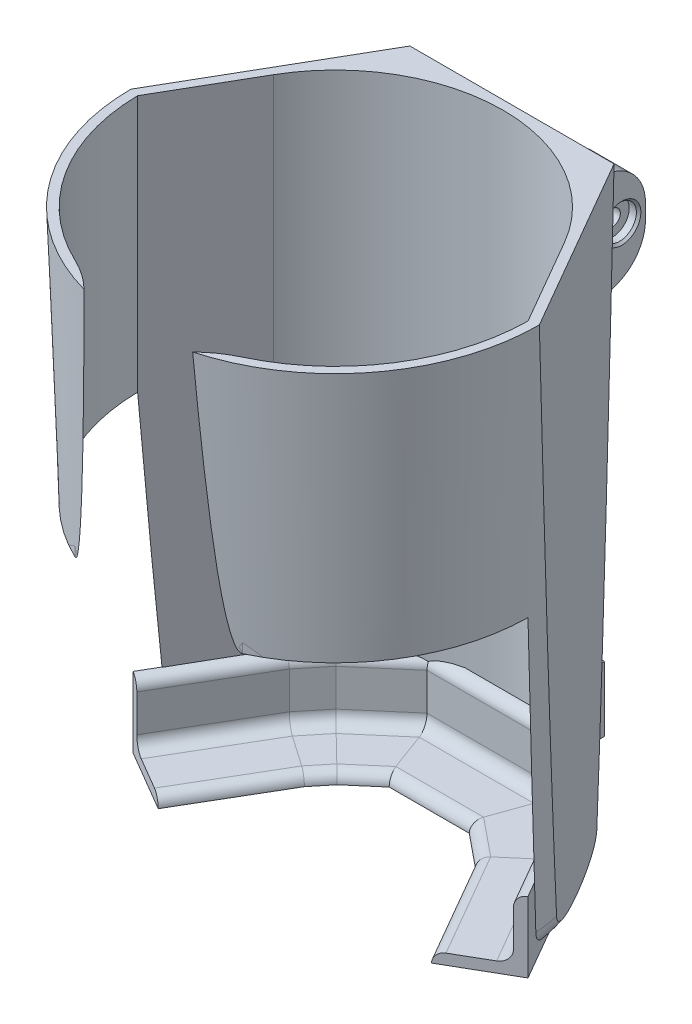
SolidWorks part; units mm, degrees
note: '?' marks a value the reader was unsure of. The reader was unsure of these and kept them because the rebuilt part matched: shared geometry of "Sketch1<3>", "Sketch1<4>", "Sketch1<9>".
ref_plane "Front Plane" through (0, 0, 0) normal (0, 0, 1) x (1, 0, 0)
ref_plane "Top Plane" through (0, 0, 0) normal (0, 1, 0) x (1, 0, 0)
ref_plane "Right Plane" through (0, 0, 0) normal (1, 0, 0) x (0, 0, -1)
sketch "Sketch1" plane through (0, 0, 0) normal (0, 1, 0) x (1, 0, 0)
  line L0 (55.2877, -0.6735) -> (27.4494, 47.5438)
  line L1 (57.8318, 0) -> (28.9159, 50.0838)
  line L2 (28.9159, 50.0838) -> (-28.9159, 50.0838)
  line L3 (-28.9159, 50.0838) -> (-57.8318, 0)
  line L7 (0, -50.0838) -> (28.9159, -50.0838) [skipped]
  line L8 (43.3739, -25.0419) -> (57.8318, 0) [skipped]
  line L9 (-57.8318, 0) -> (-43.3739, -25.0419) [skipped]
  line L10 (27.4494, 47.5438) -> (-27.4494, 47.5438)
  line L11 (-27.4494, 47.5438) -> (-55.2877, -0.6735)
  line L12 (0, -2.9319) -> (0, 50.0838) construction
  line L13 (-55.2877, -0.6735) -> (55.2877, -0.6735)
  arc A0 (-57.8318, 0) -> (57.8318, 0) centre (0, 0) ccw
  arc A1 (43.3739, 25.0419) -> (-43.3739, 25.0419) centre (0, 0) ccw construction
  arc A2 (-55.2877, -0.6735) -> (55.2877, -0.6735) centre (0, 0) ccw
  arc A3 (41.1742, 23.7719) -> (-41.1742, 23.7719) centre (0, 0) ccw
  arc A4 (-55.2877, -0.6735) -> (-23.6852, -49.962) centre (0, 0) ccw
  arc A5 (-23.6852, -49.962) -> (-15.381, -55.7489) centre (-36.8096, -77.6469) cw
  arc A6 (23.6852, -49.962) -> (15.381, -55.7489) centre (36.8096, -77.6469) ccw
  arc A7 (55.2877, -0.6735) -> (23.6852, -49.962) centre (0, 0) cw
  dimension "D1" = 115.6636
  dimension "D2" = 2.54
ref_axis "Axis2" through (0, 0, 0) along (0, 1, 0)?
ref_plane "Plane1" through (0, 0, 0) normal (0, 0, 1) x (1, 0, 0)
sketch "Sketch2" plane through (0, 0, 0) normal (0, 0, 1) x (1, 0, 0)
  line L0 (-57.8318, 0) -> (-52.4478, -154.178)
  line L1 (57.8318, 0) -> (-57.8318, 0) construction
  line L2 (-28.9159, 0) -> (-57.8318, 0) construction
  line L3 (-44.6574, -161.7011) -> (0, -161.7011)
  line L5 (0, 0) -> (-57.8318, 0)
  line L6 (0, -161.7011) -> (0, 0) construction
  line L7 (27.4494, 0) -> (-27.4494, 0) construction
  line L8 (0, 0) -> (0, -161.7011)
  arc A1 (-44.6574, -161.7011) -> (-52.4478, -154.178) centre (-44.6574, -153.906) cw
  point P11 (52.1851, -161.7011)
  point P14 (-52.1851, -161.7011)
  dimension "D1" = 92
  dimension "D4" = 161.7011
revolve "Revolve11" add sketch "Sketch2" angle 360 about L6
extrude "Cut-Extrude2" cut sketch "Sketch1" against normal blind 165.1 flip side to cut contours L1 L2 L3 A0
sketch "Sketch3" plane through (0, 0, 0) normal (0, 1, 0) x (1, 0, 0)
  circle A0 centre (0, 0) radius 46.5032
  circle A1 centre (0, 0) radius 49.0432 construction
  circle A2 centre (0, 0) radius 49.0432
  dimension "D1" = 93.0063
  dimension "D2" = 2.54
ref_plane "Plane2" through (0, 6.35, 0) normal (0, 1, 0) x (1, 0, 0)
extrude "Boss-Extrude1" add sketch "Sketch1<3>" against normal blind 149.606 contours A7 L13 A4 A5 A0 A6
sketch "Sketch1<3>" plane through (0, 0, 0) normal (0, 1, 0) x (1, 0, 0) same geometry as "Sketch1"
extrude "Cut-Extrude9" cut sketch "Sketch1<4>" along direction (0, -1, 0) on the side against the normal blind 208.788 and the other way through all contours A6 A2 A5 A0 | L13 A2
sketch "Sketch1<4>" plane through (0, 0, 0) normal (0, 1, 0) x (1, 0, 0) same geometry as "Sketch1"
extrude "Cut-Extrude10" cut sketch "Sketch1<9>" against normal blind 208.788 contours L0 A3 L11 L13
sketch "Sketch1<9>" plane through (0, 0, 0) normal (0, 1, 0) x (1, 0, 0) same geometry as "Sketch1"
sketch "Sketch8" plane through (0, 0, -50.0838) normal (0, 0, -1) x (-1, 0, 0)
  circle A0 centre (0, -51.33) radius 6.0141
  circle A1 centre (0, -85.9373) radius 12.9991
ref_plane "Plane3" through (0, -120.65, 0) normal (0, 1, 0) x (1, 0, 0)
sketch "Sketch11" plane through (0, -120.65, 0) normal (0, 1, 0) x (1, 0, 0)
  line L0 (42.0229, 38.8546) -> (26.8022, 59.1891)
  line L1 (26.8022, 59.1891) -> (-23.2093, 59.1891)
  line L2 (-23.2093, 59.1891) -> (-32.2748, 47.0778)
  line L3 (-32.2748, 47.0778) -> (-54.4116, 16.7461)
  dimension "D1" = 233.184
  dimension "D2" = 233.184
  dimension "D3" = 25.4
ref_plane "Plane4" through (42.0229, -120.65, -38.8546) normal (-0.5992, 0, -0.8006) x (-0.8006, 0, 0.5992)
ref_plane "Plane6" through (0, -161.147, 0) normal (0, -1, 0) x (-1, 0, 0)
sketch "Sketch114" plane through (0, -161.147, 0) normal (0, -1, 0) x (-1, 0, 0)
  line L0 (-55.2877, -0.6735) -> (-36.4433, 31.966)
  line L1 (-55.2877, -0.6735) -> (-27.4494, 47.5438) construction
  line L2 (-36.4433, 31.966) -> (-18.596, 46.5035)
  line L3 (-18.596, 46.5035) -> (18.596, 46.5035)
  line L4 (18.596, 46.5035) -> (33.5369, 33.7)
  line L5 (33.5369, 33.7) -> (39.7875, 26.0264)
  line L6 (39.7875, 26.0264) -> (55.8624, -1.3962)
  arc A0 (43.3739, 25.0419) -> (-43.3739, 25.0419) centre (0, 0) ccw construction
  arc A1 (41.1742, 23.7719) -> (-41.1742, 23.7719) centre (0, 0) ccw construction
other "Angle iron 20 X 20 X 3(1)"
ref_plane "Plane7" through (55.2877, -161.147, 0.6735) normal (-0.5, 0, -0.866) x (-0.866, 0, 0.5)
sketch "Sketch113" plane through (55.2877, -161.147, 0.6735) normal (-0.5, 0, -0.866) x (-0.866, 0, 0.5)
  line L0 (0, 0) -> (0, 20)
  line L1 (0, 10) -> (3, 10) construction
  line L2 (3, 17) -> (3, 6.5)
  line L3 (6.5, 3) -> (17, 3)
  line L4 (10, 3) -> (10, 0) construction
  line L5 (20, 0) -> (0, 0)
  arc A0 (20, 0) -> (17, 3) centre (17, 0) ccw
  arc A1 (0, 20) -> (3, 17) centre (0, 17) cw
  arc A2 (6.5, 3) -> (3, 6.5) centre (6.5, 6.5) cw
  point P10 (10, 0)
  point P14 (0, 10)
  point P15 (3, 10)
  point P16 (10, 3)
  point P17 (3, 20)
  point P18 (20, 3)
  point P21 (0, 0)
  dimension "D2" = 3
  dimension "D3" = 20
  dimension "Radius_1" = 3.5
  dimension "D1" = 3
sketch "Sketch117" plane through (0, 0, -50.0838) normal (0, 0, -1) x (-1, 0, 0)
  line L0 (0, 0) -> (0, -161.147) construction
  line L1 (-24.6105, -5.6138) -> (-13.0259, -5.6138)
  line L2 (-24.6105, -5.6138) -> (-24.6105, -35.133)
  line L3 (-24.6105, -35.133) -> (-13.0259, -35.133)
  line L4 (-13.0259, -5.6138) -> (-13.0259, -35.133)
  line L5 (-13.0259, -136.6219) -> (-5.0316, -136.6219)
  line L6 (-13.0259, -136.6219) -> (-13.0259, -154.9814)
  line L7 (-13.0259, -154.9814) -> (-5.0316, -154.9814)
  line L8 (-5.0316, -136.6219) -> (-5.0316, -154.9814)
  line L9 (-18.596, -161.147) -> (18.596, -161.147) construction
extrude "Boss-Extrude3" add sketch "Sketch117" along normal blind 13.208 separate body
hole_wizard "CBORE for #8 Binding Head Machine Screw1" positions "3DSketch1" profile "Sketch119" counterbore size "#8" standard "ANSI Inch" end condition through all
sketch3d "3DSketch1"
  point P0 (24.6105, -19.9644, -56.5833)
sketch "Sketch119" plane through (24.6105, -19.9644, -56.5833) normal (0, 1, 0) x (0, 0, -1)
  line L0 (0, 0) -> (0, 91.2956)
  line L1 (0, 91.2956) -> (2.2479, 91.2956)
  line L3 (2.2479, 91.2956) -> (2.2479, 2.667)
  line L4 (4.7625, 2.667) -> (2.2479, 2.667)
  line L5 (4.7625, 2.667) -> (4.7625, 0.635)
  line L6 (4.7625, 0.635) -> (5.3975, 0)
  line L7 (5.3975, 0) -> (0, 0)
  line L8 (-4.7625, 0.635) -> (-5.3975, 0) construction
  line L11 (0, -6.35) -> (0, 107.95) construction
  dimension "Thru Hole Dia." = 4.4958
  dimension "Thru Hole Depth" = 91.2956
  dimension "C'Bore Dia." = 9.525
  dimension "C'Bore Depth" = 2.667
  dimension "Near C'Sink Dia." = 10.795
  dimension "Near C'Sink Angle" = 90
fillet "Fillet6" radius 12.7 2 edges at (18.8182, -35.133, -63.2918) (18.8182, -5.6138, -63.2918)
